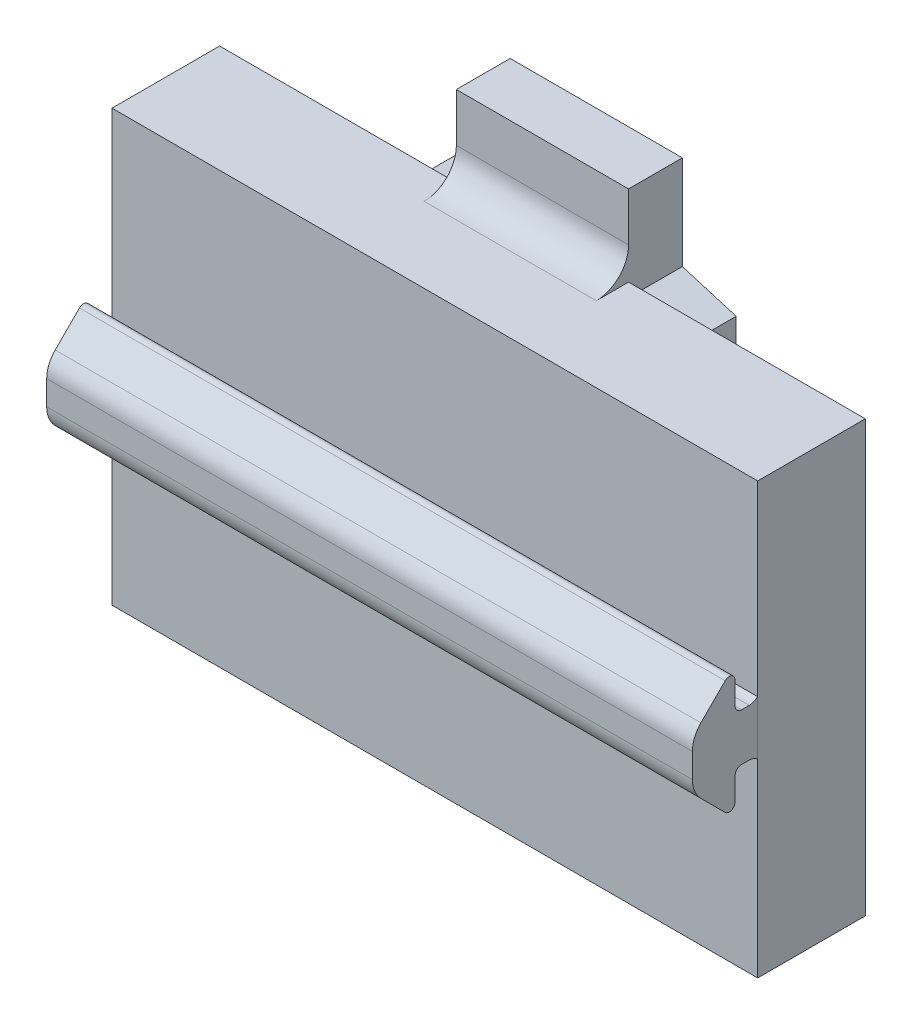
SolidWorks part; units mm, degrees
ref_plane "Front Plane" through (0, 0, 0) normal (0, 0, 1) x (1, 0, 0)
ref_plane "Top Plane" through (0, 0, 0) normal (0, 1, 0) x (1, 0, 0)
ref_plane "Right Plane" through (0, 0, 0) normal (1, 0, 0) x (0, 0, -1)
sketch "Sketch2" plane through (0, 0, 0) normal (0, 0, 1) x (1, 0, 0)
  line L0 (0, 0) -> (-7.149, 0) construction
  line L1 (-8, -27.5) -> (8, -27.5)
  line L2 (-8, -27.5) -> (-8, -18.75)
  line L3 (-8, 27.5) -> (8, 27.5)
  line L4 (8, -27.5) -> (8, -18.75)
  line L5 (-8, -27.5) -> (8, 27.5) construction
  line L6 (-8, 27.5) -> (8, -27.5) construction
  line L7 (0, 0) -> (0, 27.5) construction
  line L8 (-8, 18.75) -> (-13, 17.25)
  line L9 (-13, 17.25) -> (-13, 10.25)
  line L10 (-13, 10.25) -> (-8, 8.75)
  line L11 (8, 18.75) -> (13, 17.25)
  line L12 (13, 17.25) -> (13, 10.25)
  line L13 (13, 10.25) -> (8, 8.75)
  line L14 (8, -18.75) -> (13, -17.25)
  line L15 (13, -17.25) -> (13, -10.25)
  line L16 (13, -10.25) -> (8, -8.75)
  line L17 (-13, -10.25) -> (-8, -8.75)
  line L18 (-13, -17.25) -> (-13, -10.25)
  line L19 (-8, -18.75) -> (-13, -17.25)
  line L20 (8, 18.75) -> (8, 27.5)
  line L21 (-8, 18.75) -> (-8, 27.5)
  line L22 (-8, -8.75) -> (-8, 8.75)
  line L23 (8, -8.75) -> (8, 8.75)
  point P0 (0, 0)
  point P11 (-13, 13.75)
  point P14 (0, 13.75)
  dimension "D1" = 10
  dimension "D2" = 55
  dimension "D3" = 7
  dimension "D4" = 5
  dimension "D5" = 16
extrude "Boss-Extrude1" add sketch "Sketch2" along normal mid plane 5
sketch "Sketch3" plane through (0, 0, 2.5) normal (0, 0, 1) x (1, 0, 0)
  line L5 (-30, 20) -> (30, 20)
  line L6 (-30, 20) -> (-30, -20)
  line L7 (-30, -20) -> (30, -20)
  line L8 (30, 20) -> (30, -20)
  point P0 (0, 0)
  point P6 (0, 0)
  point P7 (-30, 0)
  dimension "D1" = 40
  dimension "D2" = 30
  dimension "D3" = 30
extrude "Boss-Extrude2" add sketch "Sketch3" along normal blind 10
sketch "Sketch5" plane through (30, 0, 0) normal (1, 0, 0) x (0, 0, -1)
  line L37 (-32.4898, 8.1206) -> (-32.4898, 3.4216)
  line L39 (-30.4832, 10.1272) -> (-25.7842, 10.1272)
  line L40 (-24.9968, 9.3398) -> (-24.9968, 8.6286)
  line L41 (-25.3016, 8.3238) -> (-27.4098, 8.3238)
  line L42 (-28.0025, 6.8929) -> (-25.7477, 4.638)
  line L43 (-29.2555, 5.6399) -> (-27.0007, 3.385)
  line L44 (-30.6864, 5.0472) -> (-30.6864, 2.939)
  line L45 (-30.9912, 2.6342) -> (-31.7024, 2.6342)
  line L46 (-23.6283, 3.7602) -> (-21.3615, 3.7602)
  line L47 (-26.1228, 1.2657) -> (-26.1228, -1.0012)
  line L48 (-13.9986, 2.6342) -> (-13.2874, 2.6342)
  line L49 (-14.3034, 5.0472) -> (-14.3034, 2.939)
  line L50 (-12.5, 8.1206) -> (-12.5, 3.4216)
  line L51 (-14.5066, 10.1272) -> (-19.2056, 10.1272)
  line L52 (-19.993, 9.3398) -> (-19.993, 8.6286)
  line L53 (-19.6882, 8.3238) -> (-17.58, 8.3238)
  line L54 (-18.867, 1.2657) -> (-18.867, -1.0012)
  line L55 (-16.9873, 6.8929) -> (-19.2421, 4.638)
  line L56 (-15.7343, 5.6399) -> (-17.9891, 3.385)
  line L57 (-30.9912, -2.3696) -> (-31.7024, -2.3696)
  line L58 (-30.6864, -4.7826) -> (-30.6864, -2.6744)
  line L59 (-29.2555, -5.3753) -> (-27.0007, -3.1205)
  line L60 (-28.0025, -6.6283) -> (-25.7477, -4.3735)
  line L61 (-25.3016, -8.0592) -> (-27.4098, -8.0592)
  line L62 (-24.9968, -9.0752) -> (-24.9968, -8.364)
  line L63 (-30.4832, -9.8626) -> (-25.7842, -9.8626)
  line L64 (-32.4898, -7.856) -> (-32.4898, -3.157)
  line L65 (-12.5, -7.856) -> (-12.5, -3.157)
  line L66 (-14.5066, -9.8626) -> (-19.2056, -9.8626)
  line L67 (-19.993, -9.0752) -> (-19.993, -8.364)
  line L68 (-19.6882, -8.0592) -> (-17.58, -8.0592)
  line L69 (-16.9873, -6.6283) -> (-19.2421, -4.3735)
  line L70 (-15.7343, -5.3753) -> (-17.9891, -3.1205)
  line L71 (-14.3034, -4.7826) -> (-14.3034, -2.6744)
  line L72 (-13.9986, -2.3696) -> (-13.2874, -2.3696)
  line L73 (-23.6283, -3.4956) -> (-21.3615, -3.4956)
  line L74 (-15.5222, 5.4277) -> (-17.777, 3.1729)
  line L75 (-18.567, 1.2657) -> (-18.567, -1.0012)
  line L76 (-15.5222, -5.1632) -> (-17.777, -2.9084)
  line L77 (-14.6034, -4.7826) -> (-14.6034, -2.6744)
  line L78 (-13.9986, -2.0696) -> (-13.2874, -2.0696)
  line L79 (-12.2, -7.856) -> (-12.2, -3.157)
  line L80 (-14.5066, -10.1626) -> (-19.2056, -10.1626)
  line L81 (-20.293, -9.0752) -> (-20.293, -8.364)
  line L82 (-19.6882, -7.7592) -> (-17.58, -7.7592)
  line L83 (-17.1994, -6.8405) -> (-19.4543, -4.5856)
  line L84 (-23.6283, -3.7956) -> (-21.3615, -3.7956)
  line L85 (-27.7904, -6.8405) -> (-25.5355, -4.5856)
  line L86 (-25.3016, -7.7592) -> (-27.4098, -7.7592)
  line L87 (-24.6968, -9.0752) -> (-24.6968, -8.364)
  line L88 (-30.4832, -10.1626) -> (-25.7842, -10.1626)
  line L89 (-32.7898, -7.856) -> (-32.7898, -3.157)
  line L90 (-30.9912, -2.0696) -> (-31.7024, -2.0696)
  line L91 (-30.3864, -4.7826) -> (-30.3864, -2.6744)
  line L92 (-29.4676, -5.1632) -> (-27.2128, -2.9084)
  line L93 (-26.4228, 1.2657) -> (-26.4228, -1.0012)
  line L94 (-29.4676, 5.4277) -> (-27.2128, 3.1729)
  line L95 (-30.3864, 5.0472) -> (-30.3864, 2.939)
  line L96 (-30.9912, 2.3342) -> (-31.7024, 2.3342)
  line L97 (-32.7898, 8.1206) -> (-32.7898, 3.4216)
  line L98 (-30.4832, 10.4272) -> (-25.7842, 10.4272)
  line L99 (-24.6968, 9.3398) -> (-24.6968, 8.6286)
  line L100 (-25.3016, 8.0238) -> (-27.4098, 8.0238)
  line L101 (-27.7904, 7.105) -> (-25.5355, 4.8502)
  line L102 (-23.6283, 4.0602) -> (-21.3615, 4.0602)
  line L103 (-17.1994, 7.105) -> (-19.4543, 4.8502)
  line L104 (-19.6882, 8.0238) -> (-17.58, 8.0238)
  line L105 (-20.293, 9.3398) -> (-20.293, 8.6286)
  line L108 (-13.9986, 2.3342) -> (-13.2874, 2.3342)
  line L109 (-14.6034, 5.0472) -> (-14.6034, 2.939)
  line L110 (-12.5185, 2.6527) -> (-12.5185, -2.3881)
  line L112 (-12.2, 8.1206) -> (-12.2, 3.4216) construction
  line L113 (-14.5066, 10.4272) -> (-19.2056, 10.4272) construction
  circle A0 centre (-22.4067, 0) radius 2.1463
  arc A1 (-32.4898, 8.1206) -> (-30.4832, 10.1272) centre (-30.4832, 8.1206) cw
  arc A2 (-29.2555, 5.6399) -> (-30.6864, 5.0472) centre (-29.8482, 5.0472) ccw
  arc A3 (-27.4098, 8.3238) -> (-28.0025, 6.8929) centre (-27.4098, 7.4856) ccw
  arc A4 (-25.7842, 10.1272) -> (-24.9968, 9.3398) centre (-25.7842, 9.3398) cw
  arc A5 (-32.4898, 3.4216) -> (-31.7024, 2.6342) centre (-31.7024, 3.4216) ccw
  arc A6 (-30.6864, 2.939) -> (-30.9912, 2.6342) centre (-30.9912, 2.939) cw
  arc A7 (-24.9968, 8.6286) -> (-25.3016, 8.3238) centre (-25.3016, 8.6286) cw
  arc A8 (-23.6283, 3.7602) -> (-25.7477, 4.638) centre (-23.6283, 6.7574) cw
  arc A9 (-26.1228, 1.2657) -> (-27.0007, 3.385) centre (-29.12, 1.2657) ccw
  arc A10 (-14.3034, 2.939) -> (-13.9986, 2.6342) centre (-13.9986, 2.939) ccw
  arc A11 (-12.5, 3.4216) -> (-13.2874, 2.6342) centre (-13.2874, 3.4216) cw
  arc A12 (-12.5, 8.1206) -> (-14.5066, 10.1272) centre (-14.5066, 8.1206) ccw
  arc A13 (-19.2056, 10.1272) -> (-19.993, 9.3398) centre (-19.2056, 9.3398) ccw
  arc A14 (-19.993, 8.6286) -> (-19.6882, 8.3238) centre (-19.6882, 8.6286) ccw
  arc A15 (-21.3615, 3.7602) -> (-19.2421, 4.638) centre (-21.3615, 6.7574) ccw
  arc A16 (-18.867, 1.2657) -> (-17.9891, 3.385) centre (-15.8698, 1.2657) cw
  arc A17 (-15.7343, 5.6399) -> (-14.3034, 5.0472) centre (-15.1416, 5.0472) cw
  arc A18 (-17.58, 8.3238) -> (-16.9873, 6.8929) centre (-17.58, 7.4856) cw
  arc A19 (-26.1228, -1.0012) -> (-27.0007, -3.1205) centre (-29.12, -1.0012) cw
  arc A20 (-23.6283, -3.4956) -> (-25.7477, -4.3735) centre (-23.6283, -6.4928) ccw
  arc A21 (-24.9968, -8.364) -> (-25.3016, -8.0592) centre (-25.3016, -8.364) ccw
  arc A22 (-30.6864, -2.6744) -> (-30.9912, -2.3696) centre (-30.9912, -2.6744) ccw
  arc A23 (-32.4898, -3.157) -> (-31.7024, -2.3696) centre (-31.7024, -3.157) cw
  arc A24 (-25.7842, -9.8626) -> (-24.9968, -9.0752) centre (-25.7842, -9.0752) ccw
  arc A25 (-27.4098, -8.0592) -> (-28.0025, -6.6283) centre (-27.4098, -7.221) cw
  arc A26 (-29.2555, -5.3753) -> (-30.6864, -4.7826) centre (-29.8482, -4.7826) cw
  arc A27 (-32.4898, -7.856) -> (-30.4832, -9.8626) centre (-30.4832, -7.856) ccw
  arc A28 (-12.5, -7.856) -> (-14.5066, -9.8626) centre (-14.5066, -7.856) cw
  arc A29 (-15.7343, -5.3753) -> (-14.3034, -4.7826) centre (-15.1416, -4.7826) ccw
  arc A30 (-17.58, -8.0592) -> (-16.9873, -6.6283) centre (-17.58, -7.221) ccw
  arc A31 (-19.2056, -9.8626) -> (-19.993, -9.0752) centre (-19.2056, -9.0752) cw
  arc A32 (-12.5, -3.157) -> (-13.2874, -2.3696) centre (-13.2874, -3.157) ccw
  arc A33 (-14.3034, -2.6744) -> (-13.9986, -2.3696) centre (-13.9986, -2.6744) cw
  arc A34 (-19.993, -8.364) -> (-19.6882, -8.0592) centre (-19.6882, -8.364) cw
  arc A35 (-21.3615, -3.4956) -> (-19.2421, -4.3735) centre (-21.3615, -6.4928) cw
  arc A36 (-18.867, -1.0012) -> (-17.9891, -3.1205) centre (-15.8698, -1.0012) ccw
  arc A37 (-18.567, 1.2657) -> (-17.777, 3.1729) centre (-15.8698, 1.2657) cw
  arc A38 (-18.567, -1.0012) -> (-17.777, -2.9084) centre (-15.8698, -1.0012) ccw
  arc A39 (-15.5222, -5.1632) -> (-14.6034, -4.7826) centre (-15.1416, -4.7826) ccw
  arc A40 (-14.6034, -2.6744) -> (-13.9986, -2.0696) centre (-13.9986, -2.6744) cw
  arc A41 (-12.2, -3.157) -> (-13.2874, -2.0696) centre (-13.2874, -3.157) ccw
  arc A42 (-12.2, -7.856) -> (-14.5066, -10.1626) centre (-14.5066, -7.856) cw
  arc A43 (-19.2056, -10.1626) -> (-20.293, -9.0752) centre (-19.2056, -9.0752) cw
  arc A44 (-20.293, -8.364) -> (-19.6882, -7.7592) centre (-19.6882, -8.364) cw
  arc A45 (-17.58, -7.7592) -> (-17.1994, -6.8405) centre (-17.58, -7.221) ccw
  arc A46 (-21.3615, -3.7956) -> (-19.4543, -4.5856) centre (-21.3615, -6.4928) cw
  arc A47 (-23.6283, -3.7956) -> (-25.5355, -4.5856) centre (-23.6283, -6.4928) ccw
  arc A48 (-27.4098, -7.7592) -> (-27.7904, -6.8405) centre (-27.4098, -7.221) cw
  arc A49 (-24.6968, -8.364) -> (-25.3016, -7.7592) centre (-25.3016, -8.364) ccw
  arc A50 (-25.7842, -10.1626) -> (-24.6968, -9.0752) centre (-25.7842, -9.0752) ccw
  arc A51 (-32.7898, -7.856) -> (-30.4832, -10.1626) centre (-30.4832, -7.856) ccw
  arc A52 (-32.7898, -3.157) -> (-31.7024, -2.0696) centre (-31.7024, -3.157) cw
  arc A53 (-30.3864, -2.6744) -> (-30.9912, -2.0696) centre (-30.9912, -2.6744) ccw
  arc A54 (-29.4676, -5.1632) -> (-30.3864, -4.7826) centre (-29.8482, -4.7826) cw
  arc A55 (-26.4228, -1.0012) -> (-27.2128, -2.9084) centre (-29.12, -1.0012) cw
  arc A56 (-26.4228, 1.2657) -> (-27.2128, 3.1729) centre (-29.12, 1.2657) ccw
  arc A57 (-29.4676, 5.4277) -> (-30.3864, 5.0472) centre (-29.8482, 5.0472) ccw
  arc A58 (-30.3864, 2.939) -> (-30.9912, 2.3342) centre (-30.9912, 2.939) cw
  arc A59 (-32.7898, 3.4216) -> (-31.7024, 2.3342) centre (-31.7024, 3.4216) ccw
  arc A60 (-32.7898, 8.1206) -> (-30.4832, 10.4272) centre (-30.4832, 8.1206) cw
  arc A61 (-25.7842, 10.4272) -> (-24.6968, 9.3398) centre (-25.7842, 9.3398) cw
  arc A62 (-24.6968, 8.6286) -> (-25.3016, 8.0238) centre (-25.3016, 8.6286) cw
  arc A63 (-27.4098, 8.0238) -> (-27.7904, 7.105) centre (-27.4098, 7.4856) ccw
  arc A64 (-23.6283, 4.0602) -> (-25.5355, 4.8502) centre (-23.6283, 6.7574) cw
  arc A65 (-21.3615, 4.0602) -> (-19.4543, 4.8502) centre (-21.3615, 6.7574) ccw
  arc A66 (-17.58, 8.0238) -> (-17.1994, 7.105) centre (-17.58, 7.4856) cw
  arc A67 (-20.293, 8.6286) -> (-19.6882, 8.0238) centre (-19.6882, 8.6286) ccw
  arc A68 (-19.2056, 10.4272) -> (-20.293, 9.3398) centre (-19.2056, 9.3398) ccw
  arc A70 (-12.2, 3.4216) -> (-13.2874, 2.3342) centre (-13.2874, 3.4216) cw
  arc A71 (-14.6034, 2.939) -> (-13.9986, 2.3342) centre (-13.9986, 2.939) ccw
  arc A72 (-15.5222, 5.4277) -> (-14.6034, 5.0472) centre (-15.1416, 5.0472) cw
  arc A73 (-12.2, 8.1206) -> (-14.5066, 10.4272) centre (-14.5066, 8.1206) ccw construction
  dimension "D1" = 0.3
extrude "Boss-Extrude3" add sketch "Sketch5" against normal through all separate body contours A72 L74 A37 L75 A38 L76 A39 L77 A40 L78 A41 L110 A70 L108 A71 L109 region at (30, 0.1323, 15.6714)
sketch "Sketch7" plane through (0, 0, 12.5) normal (0, 0, 1) x (1, 0, 0)
  line L0 (30, -20) -> (30, 20) construction
  line L1 (18, 15) -> (25, 15)
  line L2 (18, 15) -> (18, -15)
  line L3 (18, -15) -> (25, -15)
  line L4 (25, 15) -> (25, -15)
  line L5 (18, 15) -> (25, -15) construction
  line L6 (18, -15) -> (25, 15) construction
  line L7 (-25, 15) -> (-18, 15)
  line L8 (-25, 15) -> (-25, -15)
  line L9 (-25, -15) -> (-18, -15)
  line L10 (-18, 15) -> (-18, -15)
  line L11 (-25, 15) -> (-18, -15) construction
  line L12 (-25, -15) -> (-18, 15) construction
  line L13 (8, -20) -> (30, -20) construction
  line L14 (-13, 17.25) -> (-13, 10.25) construction
  line L15 (-30, 20) -> (-30, -20) construction
  line L16 (13, -17.25) -> (13, -10.25) construction
  line L17 (30, 20) -> (8, 20) construction
  point P0 (21.5, 0)
  point P5 (-21.5, 0)
  point P14 (0, 0)
  point P15 (0, 0)
  point P16 (0, 0)
  point P17 (43.4928, 0)
  point P21 (-27.1479, 0)
  point P26 (0, 0)
  point P30 (-18, 11.4032)
  point P31 (16.821, -15)
  dimension "D1" = 5
  dimension "D2" = 5
  dimension "D3" = 5
  dimension "D4" = 5
  dimension "D5" = 5
  dimension "D6" = 5
extrude "Cut-Extrude2" [suppressed] cut sketch "Sketch7" along normal blind 2.5 from surface
fillet "Fillet2" [suppressed] radius 5
fillet "Fillet3" [suppressed] radius 2.5
fillet "Fillet4" radius 3 2 edges at (0, -20, 2.5) (0, 20, 2.5)
